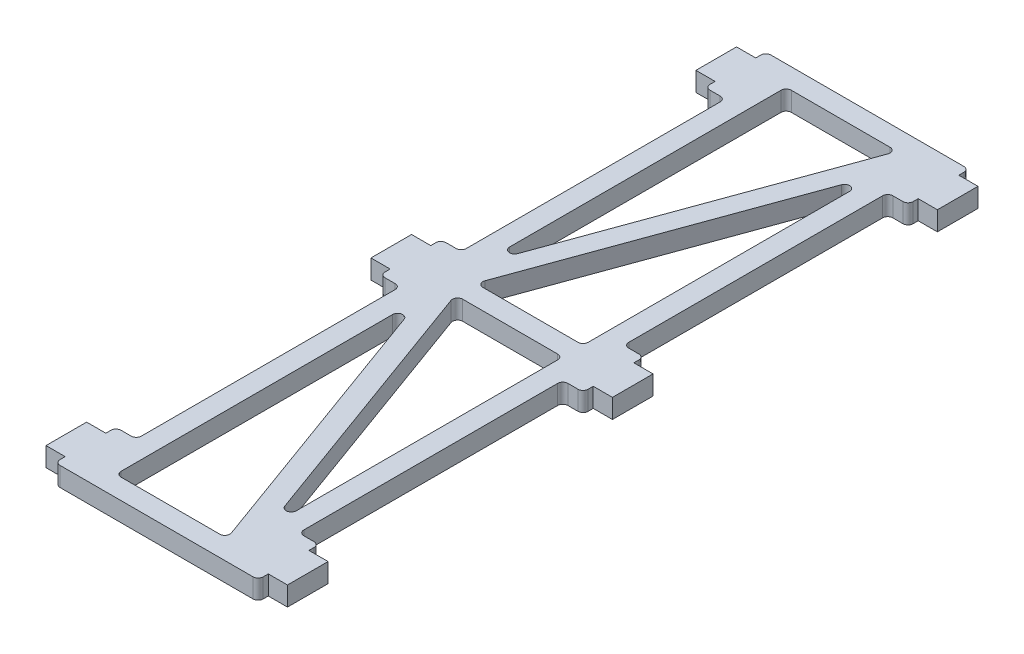
SolidWorks part; units mm, degrees
ref_plane "Front Plane" through (0, 0, 0) normal (0, 0, 1) x (1, 0, 0)
ref_plane "Top Plane" through (0, 0, 0) normal (0, 1, 0) x (1, 0, 0)
ref_plane "Right Plane" through (0, 0, 0) normal (1, 0, 0) x (0, 0, -1)
sketch "Sketch1" plane through (0, 34.29, 0) normal (0, 1, 0) x (1, 0, 0)
  line L0 (16.0528, 190.5) -> (19.05, 190.5) construction
  line L1 (0, -190.5) -> (0, 187.198) construction
  line L2 (38.1028, 187.198) -> (35.1028, 187.198) construction
  line L3 (35.1028, -190.5) -> (38.1, -190.5) construction
  line L5 (-12.7, 65.0875) -> (12.7, 65.0875)
  line L6 (-12.7, 65.0875) -> (-12.7, 176.2125)
  line L7 (-12.7, 176.2125) -> (12.7, 176.2125)
  line L8 (12.7, 65.0875) -> (12.7, 176.2125)
  line L9 (-12.7, 65.0875) -> (12.7, 176.2125) construction
  line L10 (-12.7, 176.2125) -> (12.7, 65.0875) construction
  point P0 (0, 120.65)
  dimension "D1" = 111.125
  dimension "D2" = 25.4
  dimension "D3" = 14.2875
extrude "Boss-Extrude1" add sketch "Sketch1" along normal mid plane 3 contours L7 L8 L5 L6
sketch "Sketch2" plane through (0, 35.79, 0) normal (0, 1, 0) x (1, 0, 0)
  line L0 (0, 176.2125) -> (0, 65.0186) construction
  line L1 (-12.7, 176.2125) -> (12.7, 176.2125) construction
  line L2 (12.7, 120.65) -> (-12.7, 120.65) construction
  line L3 (12.7, 65.0875) -> (12.7, 176.2125) construction
  line L4 (-12.7, 65.0875) -> (-12.7, 176.2125) construction
  line L5 (-15.875, 176.2125) -> (-12.7, 166.6875) construction
  line L6 (15.875, 166.6875) -> (12.7, 166.6875)
  line L7 (15.875, 166.6875) -> (15.875, 176.2125)
  line L8 (15.875, 176.2125) -> (12.7, 176.2125)
  line L9 (12.7, 166.6875) -> (12.7, 176.2125)
  line L10 (15.875, 166.6875) -> (12.7, 176.2125) construction
  line L11 (15.875, 176.2125) -> (12.7, 166.6875) construction
  line L12 (-15.875, 166.6875) -> (-12.7, 176.2125) construction
  line L13 (-12.7, 166.6875) -> (-12.7, 176.2125)
  line L14 (-15.875, 176.2125) -> (-12.7, 176.2125)
  line L15 (-15.875, 166.6875) -> (-15.875, 176.2125)
  line L16 (-15.875, 166.6875) -> (-12.7, 166.6875)
  line L17 (15.875, 115.8875) -> (12.7, 115.8875)
  line L18 (15.875, 115.8875) -> (15.875, 125.4125)
  line L19 (15.875, 125.4125) -> (12.7, 125.4125)
  line L20 (12.7, 115.8875) -> (12.7, 125.4125)
  line L21 (15.875, 115.8875) -> (12.7, 125.4125) construction
  line L22 (15.875, 125.4125) -> (12.7, 115.8875) construction
  line L23 (-12.7, 115.8875) -> (-12.7, 125.4125)
  line L24 (-15.875, 125.4125) -> (-12.7, 125.4125)
  line L25 (-15.875, 115.8875) -> (-15.875, 125.4125)
  line L26 (-15.875, 115.8875) -> (-12.7, 115.8875)
  line L27 (-15.875, 125.4125) -> (-12.7, 115.8875) construction
  line L28 (-15.875, 115.8875) -> (-12.7, 125.4125) construction
  line L29 (15.875, 65.0875) -> (12.7, 65.0875)
  line L30 (15.875, 65.0875) -> (15.875, 74.6125)
  line L31 (15.875, 74.6125) -> (12.7, 74.6125)
  line L32 (12.7, 65.0875) -> (12.7, 74.6125)
  line L33 (15.875, 65.0875) -> (12.7, 74.6125) construction
  line L34 (15.875, 74.6125) -> (12.7, 65.0875) construction
  line L35 (-12.7, 65.0875) -> (-12.7, 74.6125)
  line L36 (-15.875, 74.6125) -> (-12.7, 74.6125)
  line L37 (-15.875, 65.0875) -> (-15.875, 74.6125)
  line L38 (-15.875, 65.0875) -> (-12.7, 65.0875)
  line L39 (-15.875, 74.6125) -> (-12.7, 65.0875) construction
  line L40 (-15.875, 65.0875) -> (-12.7, 74.6125) construction
  point P11 (14.2875, 171.45)
  point P21 (-14.2875, 171.45)
  point P24 (14.2875, 120.65)
  point P33 (-14.2875, 120.65)
  point P34 (14.2875, 69.85)
  point P43 (-14.2875, 69.85)
  dimension "D1" = 3.175
  dimension "D2" = 9.525
  dimension "D3" = 3
extrude "Boss-Extrude2" add sketch "Sketch2" against normal up to surface (3 mm away) up to face at (0, 32.79, -120.65)
sketch "Sketch4" plane through (0, 35.79, 0) normal (0, 1, 0) x (1, 0, 0)
  line L0 (12.7, 125.4125) -> (12.7, 166.6875) construction
  line L1 (-9.525, 173.0375) -> (9.525, 173.0375)
  line L2 (-9.525, 173.0375) -> (-9.525, 68.2625)
  line L3 (-9.525, 68.2625) -> (9.525, 68.2625)
  line L4 (9.525, 173.0375) -> (9.525, 68.2625)
  line L5 (-9.525, 173.0375) -> (9.525, 68.2625) construction
  line L6 (-9.525, 68.2625) -> (9.525, 173.0375) construction
  line L7 (-12.7, 125.4125) -> (-12.7, 166.6875) construction
  line L8 (-15.875, 176.2125) -> (15.875, 176.2125) construction
  line L9 (-15.875, 65.0875) -> (15.875, 65.0875) construction
  line L10 (-9.525, 120.65) -> (9.525, 120.65) construction
  line L11 (9.525, 120.65) -> (-9.525, 173.0375) construction
  line L12 (9.525, 120.65) -> (-9.525, 68.2625) construction
  line L13 (-9.525, 120.65) -> (9.525, 173.0375) construction
  line L14 (9.525, 68.2625) -> (-9.525, 120.65) construction
  line L15 (-9.525, 119.0625) -> (9.525, 119.0625)
  line L16 (-9.525, 122.2375) -> (9.525, 122.2375)
  line L17 (11.0169, 68.805) -> (-7.8358, 120.65)
  line L18 (-7.8358, 120.65) -> (11.0169, 172.495)
  line L19 (11.2142, 120.65) -> (-8.0331, 67.72) construction
  line L20 (11.2142, 120.65) -> (-8.0331, 173.58) construction
  line L21 (8.0331, 67.72) -> (-11.2142, 120.65)
  line L22 (-11.2142, 120.65) -> (8.0331, 173.58)
  line L23 (7.8358, 120.65) -> (-11.0169, 68.805) construction
  line L24 (7.8358, 120.65) -> (-11.0169, 172.495) construction
  point P0 (0, 120.65)
  dimension "D1" = 3.175
  dimension "D2" = 3.175
  dimension "D3" = 3.175
  dimension "D4" = 3.175
  dimension "D5" = 1.5875
  dimension "D6" = 1.5875
  dimension "D7" = 1.5875
  dimension "D8" = 1.5875
extrude "Cut-Extrude1" cut sketch "Sketch4" against normal blind 3 contours L2 L22 L1 | L18 L16 L4 | L17 L4 L15 | L3 L21 L2 region at (-3.7381, 35.79, -157.1234) region at (3.9305, 35.79, -137.6224) region at (-3.7381, 35.79, -84.1766) region at (3.9305, 35.79, -103.6776)
fillet "Fillet1" radius 0.7937 32 edges at (-7.2585, 34.29, -119.0625) (-9.525, 34.29, -116.0047) (9.525, 34.29, -168.3922) (7.8358, 34.29, -173.0375) (9.525, 34.29, -72.9078) (15.875, 34.29, -65.0875) (15.875, 34.29, -74.6125) (12.7, 34.29, -74.6125) (12.7, 34.29, -115.8875) (15.875, 34.29, -115.8875) (15.875, 34.29, -125.4125) (12.7, 34.29, -125.4125) (12.7, 34.29, -166.6875) (15.875, 34.29, -166.6875) (15.875, 34.29, -176.2125) (-15.875, 34.29, -166.6875) (-12.7, 34.29, -166.6875) (-12.7, 34.29, -125.4125) (-15.875, 34.29, -125.4125) (-15.875, 34.29, -115.8875) (-12.7, 34.29, -115.8875) (-12.7, 34.29, -74.6125) (-15.875, 34.29, -74.6125) (-15.875, 34.29, -65.0875) (-9.525, 34.29, -125.2953) (7.8358, 34.29, -68.2625) (-7.2585, 34.29, -122.2375) (-15.875, 34.29, -176.2125) (9.525, 34.29, -122.2375) (9.525, 34.29, -119.0625) (-9.525, 34.29, -68.2625) (-9.525, 34.29, -173.0375)
sketch "Sketch5" plane through (0, 35.79, 0) normal (0, 1, 0) x (1, 0, 0)
  line L0 (15.875, 167.4813) -> (15.875, 175.4188) construction
  line L1 (18.875, 168.275) -> (15.875, 168.275)
  line L2 (18.875, 168.275) -> (18.875, 174.625)
  line L3 (18.875, 174.625) -> (15.875, 174.625)
  line L4 (15.875, 168.275) -> (15.875, 174.625)
  line L5 (18.875, 168.275) -> (15.875, 174.625) construction
  line L6 (18.875, 174.625) -> (15.875, 168.275) construction
  line L7 (15.875, 167.4813) -> (15.875, 175.4188) construction
  line L8 (15.875, 171.45) -> (17.375, 171.45) construction
  line L9 (0, 196.0278) -> (0, 0) construction
  line L10 (-15.875, 171.45) -> (-17.375, 171.45) construction
  line L11 (-18.875, 174.625) -> (-15.875, 168.275) construction
  line L12 (-18.875, 168.275) -> (-15.875, 174.625) construction
  line L13 (-15.875, 168.275) -> (-15.875, 174.625)
  line L14 (-18.875, 174.625) -> (-15.875, 174.625)
  line L15 (-18.875, 168.275) -> (-18.875, 174.625)
  line L16 (-18.875, 168.275) -> (-15.875, 168.275)
  line L17 (18.875, 117.475) -> (15.875, 117.475)
  line L18 (18.875, 117.475) -> (18.875, 123.825)
  line L19 (18.875, 123.825) -> (15.875, 123.825)
  line L20 (15.875, 117.475) -> (15.875, 123.825)
  line L21 (18.875, 117.475) -> (15.875, 123.825) construction
  line L22 (18.875, 123.825) -> (15.875, 117.475) construction
  line L23 (15.875, 120.65) -> (17.375, 120.65) construction
  line L24 (-15.875, 117.475) -> (-15.875, 123.825)
  line L25 (-18.875, 123.825) -> (-15.875, 123.825)
  line L26 (-18.875, 117.475) -> (-18.875, 123.825)
  line L27 (-18.875, 117.475) -> (-15.875, 117.475)
  line L28 (-15.875, 120.65) -> (-17.375, 120.65) construction
  line L29 (-18.875, 123.825) -> (-15.875, 117.475) construction
  line L30 (-18.875, 117.475) -> (-15.875, 123.825) construction
  line L31 (18.875, 66.675) -> (15.875, 66.675)
  line L32 (18.875, 66.675) -> (18.875, 73.025)
  line L33 (18.875, 73.025) -> (15.875, 73.025)
  line L34 (15.875, 66.675) -> (15.875, 73.025)
  line L35 (18.875, 66.675) -> (15.875, 73.025) construction
  line L36 (18.875, 73.025) -> (15.875, 66.675) construction
  line L37 (15.875, 69.85) -> (17.375, 69.85) construction
  line L38 (-15.875, 66.675) -> (-15.875, 73.025)
  line L39 (-18.875, 73.025) -> (-15.875, 73.025)
  line L40 (-18.875, 66.675) -> (-18.875, 73.025)
  line L41 (-18.875, 66.675) -> (-15.875, 66.675)
  line L42 (-15.875, 69.85) -> (-17.375, 69.85) construction
  line L43 (-18.875, 73.025) -> (-15.875, 66.675) construction
  line L44 (-18.875, 66.675) -> (-15.875, 73.025) construction
  line L45 (-17.375, 171.45) -> (-17.375, 120.65) construction
  point P0 (17.375, 171.45)
  point P7 (17.375, 120.65)
  point P21 (-17.375, 171.45)
  point P35 (-17.375, 120.65)
  point P36 (17.375, 69.85)
  point P49 (-17.375, 69.85)
  dimension "D1" = 3
  dimension "D2" = 6.35
  dimension "D4" = 50.8
  dimension "D3" = 3
extrude "Boss-Extrude3" add sketch "Sketch5" against normal up to surface (3 mm away) up to face at (-3.6028, 32.79, -83.0777)
